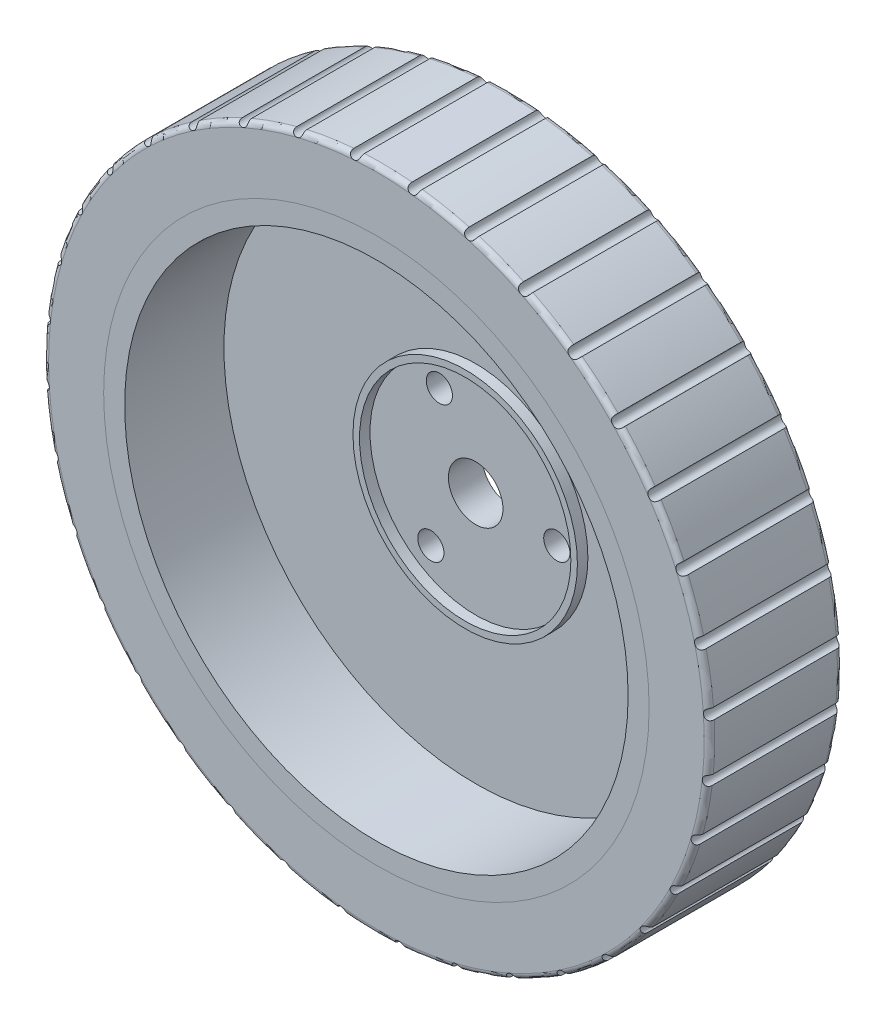
SolidWorks part; units mm, degrees
ref_plane "Front Plane" through (0, 0, 0) normal (0, 0, 1) x (1, 0, 0)
ref_plane "Top Plane" through (0, 0, 0) normal (0, 1, 0) x (1, 0, 0)
ref_plane "Right Plane" through (0, 0, 0) normal (1, 0, 0) x (0, 0, -1)
sketch "Sketch1" plane through (0, 0, 0) normal (0, 0, 1) x (1, 0, 0)
  circle A0 centre (0, 0) radius 63.5
  circle A1 centre (0, 0) radius 52
  dimension "D1" = 127
  dimension "D2" = 104
extrude "Boss-Extrude1" add sketch "Sketch1" along normal blind 25.4
fillet "Fillet1" radius 1 2 edges at (63.5, 0, 0) (63.5, 0, 25.4)
sketch "Sketch3" plane through (0, 0, 0) normal (0, 0, 1) x (1, 0, 0)
  circle A0 centre (-60.9957, 17.6573) radius 1
  circle A1 centre (0, 0) radius 63.5 construction
  circle A2 centre (-57.0029, 27.9808) radius 1
  circle A3 centre (-51.278, 37.4541) radius 1
  circle A4 centre (-43.9952, 45.7895) radius 1
  circle A5 centre (-35.3755, 52.7335) radius 1
  circle A6 centre (-25.681, 58.0753) radius 1
  circle A7 centre (-15.2062, 61.6524) radius 1
  circle A8 centre (-4.2694, 63.3563) radius 1
  circle A9 centre (6.7972, 63.1352) radius 1
  circle A10 centre (17.6573, 60.9957) radius 1
  circle A11 centre (27.9808, 57.0029) radius 1
  circle A12 centre (37.4541, 51.278) radius 1
  circle A13 centre (45.7895, 43.9952) radius 1
  circle A14 centre (52.7335, 35.3755) radius 1
  circle A15 centre (58.0753, 25.681) radius 1
  circle A16 centre (61.6524, 15.2062) radius 1
  circle A17 centre (63.3563, 4.2694) radius 1
  circle A18 centre (63.1352, -6.7972) radius 1
  circle A19 centre (60.9957, -17.6573) radius 1
  circle A20 centre (57.0029, -27.9808) radius 1
  circle A21 centre (51.278, -37.4541) radius 1
  circle A22 centre (43.9952, -45.7895) radius 1
  circle A23 centre (35.3755, -52.7335) radius 1
  circle A24 centre (25.681, -58.0753) radius 1
  circle A25 centre (15.2062, -61.6524) radius 1
  circle A26 centre (4.2694, -63.3563) radius 1
  circle A27 centre (-6.7972, -63.1352) radius 1
  circle A28 centre (-17.6573, -60.9957) radius 1
  circle A29 centre (-27.9808, -57.0029) radius 1
  circle A30 centre (-37.4541, -51.278) radius 1
  circle A31 centre (-45.7895, -43.9952) radius 1
  circle A32 centre (-52.7335, -35.3755) radius 1
  circle A33 centre (-58.0753, -25.681) radius 1
  circle A34 centre (-61.6524, -15.2062) radius 1
  circle A35 centre (-63.3563, -4.2694) radius 1
  circle A36 centre (-63.1352, 6.7972) radius 1
  point P77 (0, 0)
  dimension "D1" = 2
  dimension "D2" = 36
extrude "Cut-Extrude3" cut sketch "Sketch3" along normal through all
sketch "Sketch4" plane through (0, 0, 0) normal (0, 0, 1) x (1, 0, 0)
  circle A0 centre (0, 0) radius 52
  circle A1 centre (0, 0) radius 48
  dimension "D1" = 104
  dimension "D2" = 96
extrude "Boss-Extrude2" add sketch "Sketch4" along normal blind 25.4 separate body
sketch "Sketch5" plane through (0, 0, 0) normal (0, 0, 1) x (1, 0, 0)
  circle A0 centre (0, 0) radius 48
  dimension "D1" = 96
extrude "Boss-Extrude3" add sketch "Sketch5" along normal blind 6.47 separate body
sketch "Sketch7" plane through (0, 0, 6.47) normal (0, 0, 1) x (1, 0, 0)
  circle A0 centre (0, 0) radius 21.4
  circle A1 centre (0, 0) radius 20.15
  dimension "D1" = 42.8
  dimension "D2" = 40.3
extrude "Boss-Extrude4" add sketch "Sketch7" along normal blind 2 separate body
sketch "Sketch8" plane through (0, 0, 0) normal (0, 0, 1) x (1, 0, 0)
  circle A0 centre (0, 0) radius 5.2
  circle A1 centre (-6.926, 13.8665) radius 2.5
  circle A2 centre (15.4718, -0.9352) radius 2.5
  circle A3 centre (-8.5458, -12.9314) radius 2.5
  point P11 (0, 0)
  dimension "D1" = 3
  dimension "D2" = 5
  dimension "D3" = 10.4
  dimension "D4" = 15.5
extrude "Cut-Extrude4" cut sketch "Sketch8" against normal through all both and the other way through all
sketch "Sketch10" plane through (0, 0, 0) normal (0, 0, 1) x (1, 0, 0)
  line L0 (5.17, 20.3537) -> (11.3247, 44.5842)
  line L1 (-9.1226, 18.915) -> (-19.9829, 41.4329)
  line L2 (20.9551, 1.3727) -> (45.9016, 3.0068)
  line L3 (15.1702, 14.5212) -> (33.23, 31.8083)
  line L4 (7.781, -19.5053) -> (17.044, -42.7259)
  line L5 (18.4983, -9.9404) -> (40.5201, -21.7742)
  line L6 (-16.1462, -13.4276) -> (-35.3678, -29.4128)
  line L7 (-3.7376, -20.6647) -> (-8.1871, -45.2656)
  line L8 (-17.7599, 11.2066) -> (-38.9025, 24.5477)
  line L9 (-20.8083, -2.8311) -> (-45.5801, -6.2014)
  arc A0 (11.3247, 44.5842) -> (-19.9829, 41.4329) centre (0, 0) ccw
  arc A1 (5.17, 20.3537) -> (-9.1226, 18.915) centre (0, 0) ccw
  arc A2 (45.9016, 3.0068) -> (33.23, 31.8083) centre (0, 0) ccw
  arc A3 (20.9551, 1.3727) -> (15.1702, 14.5212) centre (0, 0) ccw
  arc A4 (17.044, -42.7259) -> (40.5201, -21.7742) centre (0, 0) ccw
  arc A5 (7.781, -19.5053) -> (18.4983, -9.9404) centre (0, 0) ccw
  arc A6 (-35.3678, -29.4128) -> (-8.1871, -45.2656) centre (0, 0) ccw
  arc A7 (-16.1462, -13.4276) -> (-3.7376, -20.6647) centre (0, 0) ccw
  arc A8 (-38.9025, 24.5477) -> (-45.5801, -6.2014) centre (0, 0) ccw
  arc A9 (-17.7599, 11.2066) -> (-20.8083, -2.8311) centre (0, 0) ccw
  point P25 (0, 0)
  dimension "D1" = 92
  dimension "D2" = 42
  dimension "D3" = 40
  dimension "D4" = 5
extrude "Cut-Extrude7" cut sketch "Sketch10" against normal blind 2.47 and the other way blind 2
